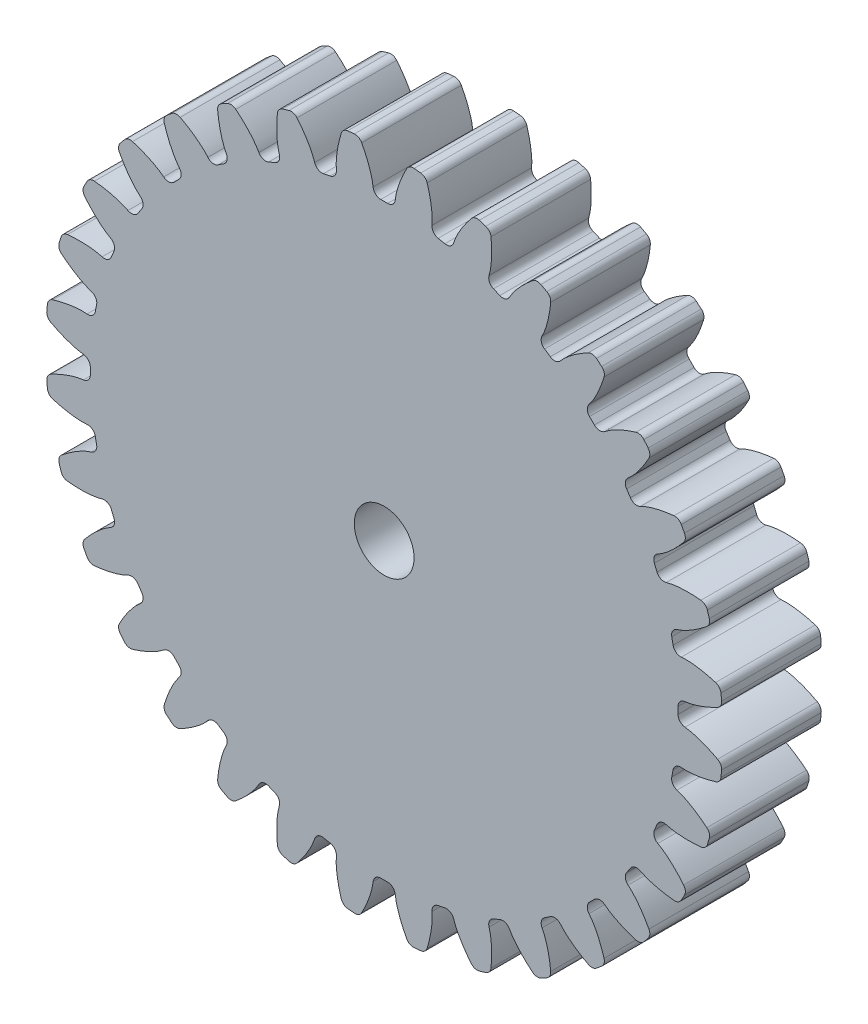
SolidWorks part; units mm, degrees
ref_plane "前视基准面" through (0, 0, 0) normal (0, 0, 1) x (1, 0, 0)
ref_plane "上视基准面" through (0, 0, 0) normal (0, 1, 0) x (1, 0, 0)
ref_plane "右视基准面" through (0, 0, 0) normal (1, 0, 0) x (0, 0, -1)
other "Configuration Table"
sketch "草图1" plane through (0, 0, 0) normal (0, 0, 1) x (1, 0, 0)
  line L0 (0, 0) -> (16, 0) construction
  line L1 (0, 0) -> (15.9807, 0.7851) construction
  line L2 (0, 0) -> (15.025, 0.5508)
  line L3 (15.9807, 0.7851) -> (15.9807, -0.7851) construction
  line L4 (0, 0) -> (15.025, -0.5508)
  circle A0 centre (0, 0) radius 17
  circle A1 centre (0, 0) radius 16 construction
  circle A2 centre (0, 0) radius 14.75
  circle A3 centre (0, 0) radius 15.0351 construction
  circle A4 centre (0, 0) radius 1.5
  spline S0 degree 4 poles (15.025, 0.5508) (15.0536, 0.5518) (15.1106, 0.5557) (15.2241, 0.5703) (15.4378, 0.6115) (15.72, 0.6883) (16.2426, 0.8744) (17.0348, 1.2631) (18.0232, 1.9245) (19.2574, 3.0372) (20.4928, 4.5428) (21.5982, 6.3745) (22.5053, 8.4934) (23.1433, 10.707) (23.5272, 12.9777) (23.6786, 15.3891) (23.554, 18.3787) (22.9491, 21.9007) (21.6561, 25.8482) (19.5595, 29.9582) (16.8951, 33.7223) (14.1416, 36.6701) (11.5294, 38.9281) (9.2078, 40.6234) (7.2723, 41.8656) (4.7663, 43.2735) (2.1575, 44.4864) (-0.5328, 45.5023) (-3.84, 46.4851) (-6.3654, 47.0454) (-8.6398, 47.4071) (-10.4928, 47.6072) (-11.359, 47.6816) (-12.2018, 47.7418) (-12.9978, 47.7823) (-13.7258, 47.8107) (-14.7402, 47.826) (-15.3884, 47.8257) (-16.4429, 47.8099) (-17.2588, 47.7748) (-18.2524, 47.722) (-19.1348, 47.6512) (-20.0863, 47.5629) (-20.9863, 47.457) (-21.6923, 47.3646) (-22.141, 47.2973) (-22.3744, 47.2622) knots 0 0 0 0 0 0.001401 0.002802 0.005604 0.010661 0.015718 0.02996 0.048734 0.068727 0.096889 0.125051 0.153212 0.181374 0.209535 0.237696 0.271429 0.327752 0.384075 0.440398 0.496721 0.553044 0.581206 0.609367 0.637529 0.66569 0.722013 0.750174 0.778336 0.834659 0.84874 0.86282 0.869861 0.876901 0.890982 0.900036 0.909091 0.920455 0.931818 0.943182 0.954545 0.965909 0.977273 0.988636 1 1 1 1 1 construction
  spline S1 degree 4 poles (15.025, 0.5508) (15.0536, 0.5518) (15.1106, 0.5557) (15.2241, 0.5703) (15.4378, 0.6115) (15.72, 0.6883) (16.2426, 0.8744) (17.0348, 1.2631) (18.0232, 1.9245) (19.2574, 3.0372) (20.4928, 4.5428) (21.5982, 6.3745) (22.5053, 8.4934) (23.1433, 10.707) (23.5272, 12.9777) (23.6786, 15.3891) (23.554, 18.3787) (22.9491, 21.9007) (21.6561, 25.8482) (19.5595, 29.9582) (16.8951, 33.7223) (14.1416, 36.6701) (11.5294, 38.9281) (9.2078, 40.6234) (7.2723, 41.8656) (4.7663, 43.2735) (2.1575, 44.4864) (-0.5328, 45.5023) (-3.84, 46.4851) (-6.3654, 47.0454) (-8.6398, 47.4071) (-10.4928, 47.6072) (-11.359, 47.6816) (-12.2018, 47.7418) (-12.9978, 47.7823) (-13.7258, 47.8107) (-14.4755, 47.822) (-14.8147, 47.8244) (-14.9827, 47.8246) knots 0 0 0 0 0 0.001401 0.002802 0.005604 0.010661 0.015718 0.02996 0.048734 0.068727 0.096889 0.125051 0.153212 0.181374 0.209535 0.237696 0.271429 0.327752 0.384075 0.440398 0.496721 0.553044 0.581206 0.609367 0.637529 0.66569 0.722013 0.750174 0.778336 0.834659 0.84874 0.86282 0.869861 0.876901 0.890982 0.900036 0.909091 0.909091 0.909091 0.909091 0.909091
  spline S2 degree 4 poles (15.025, -0.5508) (15.0536, -0.5518) (15.1106, -0.5557) (15.2241, -0.5703) (15.4378, -0.6115) (15.72, -0.6883) (16.2426, -0.8744) (17.0348, -1.2631) (18.0232, -1.9245) (19.2574, -3.0372) (20.4928, -4.5428) (21.5982, -6.3745) (22.5053, -8.4934) (23.1433, -10.707) (23.5272, -12.9777) (23.6786, -15.3891) (23.554, -18.3787) (22.9491, -21.9007) (21.6561, -25.8482) (19.5595, -29.9582) (16.8951, -33.7223) (14.1416, -36.6701) (11.5294, -38.9281) (9.2078, -40.6234) (7.2723, -41.8656) (4.7663, -43.2735) (2.1575, -44.4864) (-0.5328, -45.5023) (-3.84, -46.4851) (-6.3654, -47.0454) (-8.6398, -47.4071) (-10.4928, -47.6072) (-11.359, -47.6816) (-12.2018, -47.7418) (-12.9978, -47.7823) (-13.7258, -47.8107) (-14.7402, -47.826) (-15.3884, -47.8257) (-16.4429, -47.8099) (-17.2588, -47.7748) (-18.2524, -47.722) (-19.1348, -47.6512) (-20.0863, -47.5629) (-20.9863, -47.457) (-21.6923, -47.3646) (-22.141, -47.2973) (-22.3744, -47.2622) knots 0 0 0 0 0 0.001401 0.002802 0.005604 0.010661 0.015718 0.02996 0.048734 0.068727 0.096889 0.125051 0.153212 0.181374 0.209535 0.237696 0.271429 0.327752 0.384075 0.440398 0.496721 0.553044 0.581206 0.609367 0.637529 0.66569 0.722013 0.750174 0.778336 0.834659 0.84874 0.86282 0.869861 0.876901 0.890982 0.900036 0.909091 0.920455 0.931818 0.943182 0.954545 0.965909 0.977273 0.988636 1 1 1 1 1 construction
  spline S3 degree 4 poles (15.025, -0.5508) (15.0536, -0.5518) (15.1106, -0.5557) (15.2241, -0.5703) (15.4378, -0.6115) (15.72, -0.6883) (16.2426, -0.8744) (17.0348, -1.2631) (18.0232, -1.9245) (19.2574, -3.0372) (20.4928, -4.5428) (21.5982, -6.3745) (22.5053, -8.4934) (23.1433, -10.707) (23.5272, -12.9777) (23.6786, -15.3891) (23.554, -18.3787) (22.9491, -21.9007) (21.6561, -25.8482) (19.5595, -29.9582) (16.8951, -33.7223) (14.1416, -36.6701) (11.5294, -38.9281) (9.2078, -40.6234) (7.2723, -41.8656) (4.7663, -43.2735) (2.1575, -44.4864) (-0.5328, -45.5023) (-3.84, -46.4851) (-6.3654, -47.0454) (-8.6398, -47.4071) (-10.4928, -47.6072) (-11.359, -47.6816) (-12.2018, -47.7418) (-12.9978, -47.7823) (-13.7258, -47.8107) (-14.4755, -47.822) (-14.8147, -47.8244) (-14.9827, -47.8246) knots 0 0 0 0 0 0.001401 0.002802 0.005604 0.010661 0.015718 0.02996 0.048734 0.068727 0.096889 0.125051 0.153212 0.181374 0.209535 0.237696 0.271429 0.327752 0.384075 0.440398 0.496721 0.553044 0.581206 0.609367 0.637529 0.66569 0.722013 0.750174 0.778336 0.834659 0.84874 0.86282 0.869861 0.876901 0.890982 0.900036 0.909091 0.909091 0.909091 0.909091 0.909091
  point P15 (15.9807, 0)
  dimension "齿顶圆直径" = 34
  dimension "分度圆直径" = 32
  dimension "齿根圆直径" = 29.5
  dimension "基圆直径" = 30.0702
  dimension "内孔直径" = 3
  dimension "渐近线镜像线夹角" = 2.813
extrude "凸台-拉伸1" add sketch "草图1" along normal blind 5 contours A0 | A4
extrude "切除-拉伸1" cut sketch "草图1<3>" along normal through all contours A2 S3 A0 S1 region at (16.0413, 0, 0)
sketch "草图1<3>" plane through (0, 0, 0) normal (0, 0, 1) x (1, 0, 0) same geometry as "草图1"
fillet "圆角1" radius 0.38 4 edges at (16.9539, 1.2517, 2.5) (16.9539, -1.2517, 2.5) (14.7401, 0.5404, 2.5) (14.7401, -0.5404, 2.5)
pattern_circular "阵列(圆周)1" count 32 every 11.25 about axis through (0, 0, 5) along (0, 0, 1) of "切除-拉伸1", "圆角1"
equation "\"m\"= 1'模数"
equation "\"z\"= 32'齿数"
equation "\"a\"= 20度'压力角"
equation "\"d\"= \"m\" * \"z\"'分度圆直径"
equation "\"da\"= ( \"z\" + 2 ) * \"m\"'齿顶圆直径"
equation "\"df\"= ( \"z\" - 2.5 ) * \"m\"'齿根圆直径"
equation "\"s\"= 0.5 * PI * \"m\"'分度圆齿厚"
equation "\"r\"= 0.38 * \"m\"'齿根圆角"
equation "\"B\"= 0.3 * \"d\"'齿厚"
equation "\"db\"= \"m\" * \"z\" * cos ( \"a\" )'基圆直径"
equation "\"rb\"= \"db\" / 2'基圆半径"
equation "\"齿顶圆直径@草图1\"= \"da\""
equation "\"分度圆直径@草图1\"= \"d\""
equation "\"齿根圆直径@草图1\"= \"df\""
equation "\"基圆直径@草图1\"= \"db\""
equation "\"渐近线镜像线夹角@草图1\"= 360 / 4 / \"z\""
equation "\"h\"= 5'齿轮厚度"
equation "\"ir\"= 3'内孔直径"
equation "\"内孔直径@草图1\"= \"ir\""
equation "\"齿轮厚@凸台-拉伸1\"= \"h\""
equation "\"齿轮夹角@阵列(圆周)1\"= 360 / \"z\""
equation "\"齿数@阵列(圆周)1\"= \"z\""
equation "\"D1@圆角1\"=\"m\"*0.38"
